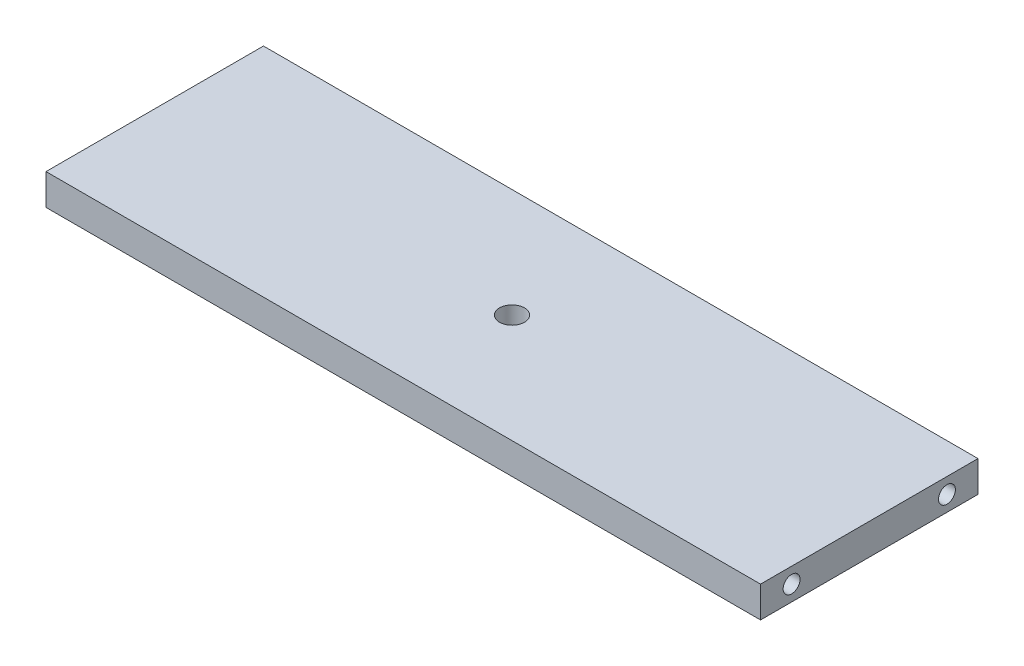
SolidWorks part; units mm, degrees
material "6061 Alloy"
ref_plane "Front Plane" through (0, 0, 0) normal (0, 0, 1) x (1, 0, 0)
ref_plane "Top Plane" through (0, 0, 0) normal (0, 1, 0) x (1, 0, 0)
ref_plane "Right Plane" through (0, 0, 0) normal (1, 0, 0) x (0, 0, -1)
sketch "Sketch2" plane through (0, 0, 0) normal (0, 1, 0) x (1, 0, 0)
  line L1 (-73.025, -22.225) -> (73.025, -22.225)
  line L2 (-73.025, -22.225) -> (-73.025, 22.225)
  line L3 (-73.025, 22.225) -> (73.025, 22.225)
  line L4 (73.025, -22.225) -> (73.025, 22.225)
  line L5 (-73.025, -22.225) -> (73.025, 22.225) construction
  line L6 (-73.025, 22.225) -> (73.025, -22.225) construction
  point P0 (0, 0)
  dimension "D1" = 146.05
  dimension "D2" = 44.45
extrude "Boss-Extrude1" add sketch "Sketch2" along normal blind 6.35
hole_wizard "1/4-20 Tapped Hole1" positions "Sketch4" profile "Sketch5" tap size "1/4-20" standard "ANSI Inch" end condition through all
sketch "Sketch4" plane through (0, 0, 0) normal (0, -1, 0) x (-1, 0, 0)
  point P0 (0, 0)
sketch "Sketch5" plane through (0, 0, 0) normal (1, 0, 0) x (0, 0, -1)
  line L0 (0, 0) -> (0, 6.35)
  line L1 (0, 6.35) -> (2.5527, 6.35)
  line L2 (2.5527, 6.35) -> (2.5527, 0)
  line L5 (2.5527, 0) -> (0, 0)
  line L11 (0, -6.35) -> (0, 107.95) construction
  dimension "Thru Tap Drill Dia." = 5.1054
  dimension "Thru Tap Drill Depth" = 6.35
cosmetic thread "Hole Thread1" parameters "D2"=6.35
hole_wizard "#8-32 Tapped Hole1" positions "Sketch6" profile "Sketch7" tap size "#8-32" standard "ANSI Inch"
sketch "Sketch6" plane through (-73.025, 0, 0) normal (-1, 0, 0) x (0, 0, 1)
  line L0 (-22.225, 6.35) -> (-22.225, 0) construction
  line L1 (22.225, 6.35) -> (22.225, 0) construction
  line L2 (-22.225, 0) -> (22.225, 0) construction
  point P0 (-15.875, 3.175)
  point P2 (15.875, 3.175)
  dimension "D1" = 6.35
  dimension "D2" = 6.35
  dimension "D3" = 3.175
  dimension "D4" = 3.175
sketch "Sketch7" plane through (-73.025, 3.175, -15.875) normal (0, 1, 0) x (0, 0, 1)
  line L0 (0, 0) -> (0, 7.3878)
  line L1 (0, 7.3878) -> (1.7272, 6.35)
  line L2 (1.7272, 6.35) -> (1.7272, 0)
  line L5 (1.7272, 0) -> (0, 0)
  line L10 (0, 7.3878) -> (-1.7272, 6.35) construction
  line L11 (0, -6.35) -> (0, 107.95) construction
  dimension "Tap Drill Dia." = 3.4544
  dimension "Tap Drill Depth" = 6.35
  dimension "Drill Angle" = 118
cosmetic thread "Hole Thread2" parameters "D1"=6.35, "D2"=4.1656
cosmetic thread "Hole Thread3" parameters "D1"=6.35, "D2"=4.1656
mirror "Mirror1" about plane through (0, 0, 0) normal (1, 0, 0) of "#8-32 Tapped Hole1"
